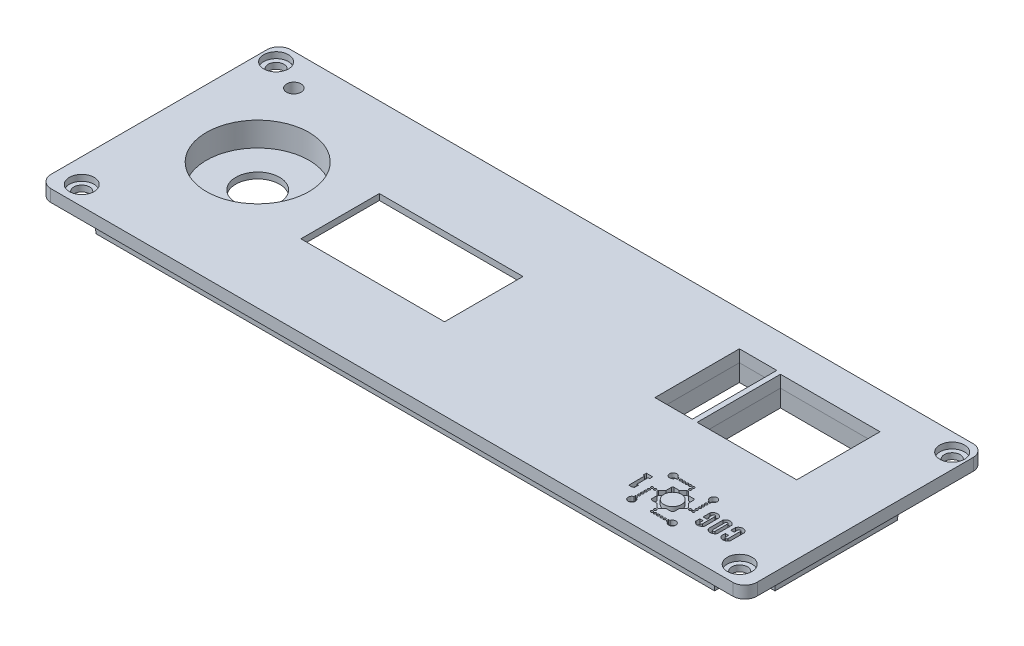
SolidWorks part; units mm, degrees
other "Markup1"
sketch "Sketch25" plane through (-58.5, 2, 19.9) normal (-0.4493, 0.8869, 0.1077) x (-0.8892, -0.4555, 0.042)
other "Markup2"
sketch "Sketch36" plane through (-58.5, -3, -19.8) normal (-0.1656, -0.3822, -0.9091) x (0.9836, -0.1306, -0.1243)
ref_plane "Front Plane" through (0, 0, 0) normal (0, 0, 1) x (1, 0, 0)
ref_plane "Top Plane" through (0, 0, 0) normal (0, 1, 0) x (1, 0, 0)
ref_plane "Right Plane" through (0, 0, 0) normal (1, 0, 0) x (0, 0, -1)
sketch "Sketch1" plane through (0, 0, 0) normal (0, 1, 0) x (1, 0, 0)
  line L0 (58.5, 17.9) -> (58.5, -17.9)
  line L1 (-56.5, 17.9) -> (56.5, 17.9) construction
  line L2 (-56.5, 17.9) -> (-56.5, -17.9) construction
  line L3 (-56.5, -17.9) -> (56.5, -17.9) construction
  line L4 (56.5, 17.9) -> (56.5, -17.9) construction
  line L5 (0, -17.9) -> (0, 17.9) construction
  line L6 (-56.5, 0) -> (56.5, 0) construction
  line L7 (-58.5, 17.9) -> (-58.5, -17.9)
  line L8 (-56.5, -20) -> (56.5, -20)
  line L9 (-56.5, 19.8) -> (56.5, 19.8)
  arc A0 (-56.5, 19.8) -> (-58.5, 17.9) centre (-56.5, 17.7974) ccw
  arc A1 (56.5, 19.8) -> (58.5, 17.9) centre (56.5, 17.7974) cw
  arc A2 (56.5, -20) -> (58.5, -17.9) centre (56.5, -17.9976) ccw
  arc A3 (-58.5, -17.9) -> (-56.5, -20) centre (-56.3975, -17.9) ccw
  circle A7 centre (54.5, -16.85) radius 1.3
  circle A8 centre (56, 16.85) radius 1.3
  circle A9 centre (-56, 16.85) radius 1.3
  circle A10 centre (-54.5, -16.85) radius 1.3
  point P0 (0, 0)
  dimension "D8" = 16.85
  dimension "D1" = 35.8
  dimension "D2" = 113
  dimension "D6" = 1.9
  dimension "D7" = 16.85
  dimension "D9" = 54.5
  dimension "D10" = 56
  dimension "D3" = 2
  dimension "D4" = 2
  dimension "D5" = 2.1
extrude "Boss-Extrude1" add sketch "Sketch1" along normal blind 2
sketch "Sketch3" plane through (0, 0, 0) normal (0, -1, 0) x (1, 0, 0)
  line L4 (0, 0) -> (-65.5905, 0) construction
  line L5 (-51.4, 17.9) -> (51.4, 17.9)
  line L6 (-51.4, 17.9) -> (-51.4, 16.4)
  line L7 (-51.4, 16.4) -> (51.4, 16.4)
  line L8 (56.4, -17.7) -> (56.4, 17.9)
  line L9 (56.4, 17.9) -> (-56.4, 17.9)
  line L10 (-56.4, 17.9) -> (-56.4, -17.7)
  line L11 (-56.4, -17.7) -> (56.4, -17.7)
  line L12 (56.4, -17.7) -> (56.4, 17.9) construction
  line L13 (56.4, 17.9) -> (-56.4, 17.9) construction
  line L14 (-56.4, 17.9) -> (-56.4, -17.7) construction
  line L15 (-56.4, -17.7) -> (56.4, -17.7) construction
  line L16 (51.4, 17.9) -> (51.4, 16.4)
  line L17 (51.4, -17.9) -> (51.4, -16.4)
  line L18 (-51.4, -16.4) -> (51.4, -16.4)
  line L19 (-51.4, -17.9) -> (-51.4, -16.4)
  line L20 (-51.4, -17.9) -> (51.4, -17.9)
  line L21 (0, 0) -> (0, 10.6719) construction
  line L22 (-56.4, 12.9) -> (-54.9, 12.9)
  line L23 (-56.4, 12.9) -> (-56.4, -7.7)
  line L24 (-56.4, -7.7) -> (-54.9, -7.7)
  line L25 (-54.9, 12.9) -> (-54.9, -7.7)
  line L26 (54.9, 12.9) -> (54.9, -7.7)
  line L27 (56.4, -7.7) -> (54.9, -7.7)
  line L28 (56.4, 12.9) -> (56.4, -7.7)
  line L29 (56.4, 12.9) -> (54.9, 12.9)
  point P4 (-51.4, 17.15)
  dimension "D2" = 5
  dimension "D3" = 5
  dimension "D4" = 1.5
  dimension "D5" = 1.5
  dimension "D6" = 10
  dimension "D7" = 5
  dimension "D1" = 2.1
extrude "Boss-Extrude2" add sketch "Sketch3" along normal blind 3 draft 3
sketch "Sketch6" plane through (0, 2, 0) normal (0, 1, 0) x (1, 0, 0)
  circle A15 centre (-56, 16.85) radius 2.05
  circle A16 centre (-56, 16.85) radius 2.05
  circle A18 centre (-54.5, -16.85) radius 2.05
  circle A19 centre (-54.5, -16.85) radius 2.05
  circle A21 centre (54.5, -16.85) radius 2.05
  circle A22 centre (54.5, -16.85) radius 2.05
  circle A24 centre (56, 16.85) radius 2.05
  circle A25 centre (56, 16.85) radius 2.05
  dimension "D1" = 0.75
  dimension "D2" = 0.75
  dimension "D3" = 0.75
  dimension "D4" = 0.75
extrude "Cut-Extrude3" cut sketch "Sketch6" against normal blind 1
sketch "Sketch5" plane through (0, 0, 0) normal (0, -1, 0) x (1, 0, 0)
  line L0 (56.5, -19.8) -> (-56.5, -19.8) construction
  line L1 (-57.5, -10.95) -> (57.5, -10.95) construction
  line L2 (-57.5, -10.95) -> (-57.5, -12.55) construction
  line L3 (-57.5, -12.55) -> (57.5, -12.55) construction
  line L5 (-30.3, 11.9) -> (-3, 11.9) construction
  line L6 (-30.3, 11.9) -> (-30.3, -15.9) construction
  line L7 (-30.3, -15.9) -> (-3, -15.9) construction
  line L8 (-3, 11.9) -> (-3, -15.9) construction
  line L9 (-28.55, 6.5) -> (-4.75, 6.5)
  line L10 (-28.55, 6.5) -> (-28.55, -6.5)
  line L11 (-28.55, -6.5) -> (-4.75, -6.5)
  line L12 (57.5, -10.95) -> (57.5, -12.55) construction
  line L13 (0, -12.55) -> (0, -10.95) construction
  line L14 (-57.5, -11.75) -> (57.5, -11.75) construction
  line L15 (-4.75, 6.5) -> (-4.75, -6.5)
  line L16 (-16.65, -6.5) -> (-16.65, 6.5) construction
  line L17 (-28.55, 0) -> (-4.75, 0) construction
  line L18 (-30.3, 7.63) -> (-3, 7.63) construction
  line L19 (-30.3, 7.63) -> (-30.3, -11.64) construction
  line L20 (-30.3, -11.64) -> (-3, -11.64) construction
  line L21 (-3, 7.63) -> (-3, -11.64) construction
  point P0 (0, -11.75)
  point P11 (-16.65, 0)
  point P16 (-16.65, 11.9)
  dimension "D1" = 115
  dimension "D2" = 1.6
  dimension "D3" = 54.5
  dimension "D4" = 27.3
  dimension "D5" = 27.8
  dimension "D6" = 7.25
  dimension "D7" = 13
  dimension "D8" = 23.8
  dimension "D9" = 1.13
  dimension "D10" = 19.27
  dimension "D11" = 4.27
sketch "Sketch8" plane through (0, 0, 0) normal (0, -1, 0) x (1, 0, 0)
  line L1 (-30.3, 11.9) -> (-3, 11.9)
  line L2 (-30.3, 11.9) -> (-30.3, -15.9)
  line L3 (-30.3, -15.9) -> (-3, -15.9)
  line L4 (-3, 11.9) -> (-3, -15.9)
extrude "Boss-Extrude16" add sketch "Sketch8" along normal blind 0.5
sketch "Sketch9" plane through (0, -0.5, 0) normal (0, -1, 0) x (1, 0, 0)
  line L0 (-30.4, 7.73) -> (-23.8, 7.73)
  line L1 (-23.8, 7.73) -> (-23.8, 11.9)
  line L2 (-30.3, 11.9) -> (-3, 11.9) construction
  line L3 (-23.8, 11.9) -> (-9.5, 11.9)
  line L4 (-3, 11.9) -> (-3, -15.9) construction
  line L6 (-30.4, 7.73) -> (-30.4, -11.84)
  line L8 (-2.9, 7.73) -> (-2.9, -11.84)
  line L9 (-9.5, 11.9) -> (-9.5, 7.73)
  line L11 (-30.3, 11.9) -> (-30.3, -15.9) construction
  line L16 (-9.5, 7.73) -> (-2.9, 7.73)
  line L18 (-30.3, 7.63) -> (-3, 7.63) construction
  line L19 (-30.4, -11.84) -> (-23.8, -11.84)
  line L20 (-23.8, -11.84) -> (-23.8, -15.9)
  line L21 (-30.3, -15.9) -> (-3, -15.9) construction
  line L22 (-23.8, -15.9) -> (-9.5, -15.9)
  line L23 (-9.5, -15.9) -> (-9.5, -11.84)
  line L24 (-9.5, -11.84) -> (-2.9, -11.84)
  dimension "D1" = 0.1
  dimension "D3" = 0.1
  dimension "D4" = 0.1
  dimension "D5" = 6.5
  dimension "D6" = 6.5
extrude "Cut-Extrude8" cut sketch "Sketch9" against normal blind 1.5
sketch "Sketch10" plane through (0, 1, 0) normal (0, -1, 0) x (1, 0, 0)
  line L8 (-4.75, -6.5) -> (-4.75, 6.5)
  line L9 (-28.55, -6.5) -> (-4.75, -6.5)
  line L10 (-28.55, 6.5) -> (-28.55, -6.5)
  line L11 (-4.75, 6.5) -> (-28.55, 6.5)
  line L12 (-4.75, -6.5) -> (-4.75, 6.5)
  line L13 (-28.55, -6.5) -> (-4.75, -6.5)
  line L14 (-28.55, 6.5) -> (-28.55, -6.5)
  line L15 (-4.75, 6.5) -> (-28.55, 6.5)
  dimension "D1" = 0
extrude "Cut-Extrude9" cut sketch "Sketch10" against normal up to surface (1 mm away) up to face at (-56, 2, -14.8)
sketch "Sketch11" plane through (0, -0.5, 0) normal (0, -1, 0) x (1, 0, 0)
  line L1 (-30.3, 11.9) -> (-30.3, -15.9) construction
  line L2 (-3, 11.9) -> (-3, -15.9) construction
  line L3 (-30.3, 9.9) -> (-3, 9.9) construction
  line L5 (-30.3, 11.9) -> (-3, 11.9) construction
  line L6 (-30.3, -15.9) -> (-3, -15.9) construction
  line L7 (-5, -15.9) -> (-5, 11.9) construction
  line L8 (-16.65, 6.5) -> (-16.65, -8.5129) construction
  circle A0 centre (-5, 9.9) radius 0.8
  circle A3 centre (-28.3, 9.9) radius 0.8
  dimension "D4" = 1.6
  dimension "D1" = 2
  dimension "D3" = 2
extrude "Boss-Extrude6" add sketch "Sketch11" along normal blind 1.2
fillet "Fillet1" radius 0.6 2 edges at (-5, -1.7, 9.1) (-28.3, -1.7, 10.7)
sketch "Sketch13" plane through (0, 0, 0) normal (0, -1, 0) x (1, 0, 0)
  line L0 (-57.5, -10.95) -> (-57.5, -12.55) construction
  line L1 (-57.5, -10.95) -> (57.5, -10.95) construction
  line L2 (-57.5, -12.55) -> (57.5, -12.55) construction
  circle A0 centre (-43.15, -0.95) radius 8 construction
  circle A2 centre (-43.15, -0.95) radius 8.5
  circle A4 centre (-50.77, -14.55) radius 1.2
  dimension "D2" = 16
  dimension "D8" = 2.4
  dimension "D9" = 6.73
  dimension "D1" = 14.35
  dimension "D3" = 10
  dimension "D10" = 2
  dimension "D7" = 0.5
extrude "Cut-Extrude10" cut sketch "Sketch13" against normal up to surface (2 mm away) up to face at (-16.65, 2, 0)
sketch "Sketch16" plane through (0, 2, 0) normal (0, 1, 0) x (1, 0, 0)
  line L0 (-4.3168, 26.8231) -> (81.0165, 26.8231) construction
  line L1 (50.3534, -14.2896) -> (50.3534, -11.9125)
  line L2 (48.878, -11.9125) -> (48.878, -12.6953)
  line L3 (48.878, -12.6953) -> (49.433, -12.6953)
  line L4 (49.433, -12.6953) -> (49.433, -12.0324)
  line L5 (49.8354, -12.0324) -> (49.8354, -14.1204)
  line L6 (49.433, -14.1204) -> (49.433, -13.6115)
  line L7 (49.433, -13.6115) -> (48.878, -13.6115)
  line L8 (48.878, -13.6115) -> (48.878, -14.2896)
  line L9 (48.2412, -14.2896) -> (48.2412, -11.9125)
  line L10 (46.7671, -11.9125) -> (46.7671, -14.2896)
  line L11 (47.7035, -12.0324) -> (47.7035, -14.1204)
  line L12 (47.3081, -14.1204) -> (47.3081, -12.0324)
  line L13 (46.1267, -14.2896) -> (46.1267, -11.9125)
  line L14 (44.6639, -11.9125) -> (44.6639, -13.0881)
  line L15 (44.6639, -13.0881) -> (45.3238, -13.0881)
  line L16 (45.3238, -13.0881) -> (45.3238, -12.6953)
  line L17 (45.3238, -12.6953) -> (45.2014, -12.6953)
  line L18 (45.2014, -12.6953) -> (45.2014, -12.0324)
  line L19 (45.5941, -12.0324) -> (45.5941, -14.1204)
  line L20 (45.2014, -14.1204) -> (45.2014, -13.6115)
  line L21 (45.2014, -13.6115) -> (44.6639, -13.6115)
  line L22 (44.6639, -13.6115) -> (44.6639, -14.2896)
  line L44 (40.4042, -14.9356) -> (41.3098, -14.9356)
  line L45 (41.3098, -14.9356) -> (41.4866, -14.7588)
  line L46 (41.4866, -14.7588) -> (41.4866, -13.8532)
  line L50 (42.4261, -16.72) -> (42.1504, -16.72)
  line L51 (42.1504, -16.72) -> (42.1504, -16.3239)
  line L52 (42.1504, -16.3239) -> (42.4211, -16.3239)
  line L53 (36.0066, -15.8752) -> (36.0066, -15.5994)
  line L54 (36.4027, -15.5994) -> (36.4027, -15.8701)
  line L55 (36.0066, -15.5994) -> (36.4027, -15.5994)
  line L56 (36.8515, -9.4557) -> (37.1272, -9.4557)
  line L57 (37.1272, -9.8518) -> (36.8565, -9.8518)
  line L58 (37.1272, -9.4557) -> (37.1272, -9.8518)
  line L59 (43.271, -10.3005) -> (43.271, -10.5763)
  line L60 (42.8749, -10.5763) -> (42.8749, -10.3055)
  line L61 (43.271, -10.5763) -> (42.8749, -10.5763)
  line L62 (34.7503, -11.5007) -> (34.7503, -12.0307)
  line L63 (34.7503, -12.0307) -> (34.4877, -12.0307)
  line L64 (34.4877, -12.0307) -> (34.4877, -13.8706)
  line L65 (34.4877, -13.8706) -> (34.7503, -13.8706)
  line L66 (34.7503, -13.8706) -> (34.7503, -14.5384)
  line L67 (34.7503, -14.5384) -> (34.4877, -14.6755)
  line L68 (34.4877, -14.6755) -> (33.9483, -14.6755)
  line L69 (33.9483, -14.6755) -> (33.9483, -12.0307)
  line L70 (33.9483, -12.0307) -> (33.682, -12.0307)
  line L71 (33.682, -12.0307) -> (33.682, -11.5007)
  line L72 (33.682, -11.5007) -> (34.7503, -11.5007)
  line L73 (39.6388, -13.0878) -> (40.774, -15.8285) construction
  line L74 (40.774, -15.8285) -> (40.4042, -14.9356) construction
  line L75 (39.6388, -13.0878) -> (42.5677, -14.301) construction
  line L76 (39.6388, -13.0878) -> (39.6388, -15.4936) construction
  line L77 (39.6388, -13.0878) -> (40.8661, -14.3151) construction
  line L78 (42.0125, -13.5426) -> (40.0416, -15.5135) construction
  line L79 (38.8734, -14.9356) -> (39.5138, -15.576)
  line L80 (39.5138, -15.576) -> (39.7638, -15.576)
  line L82 (37.791, -13.8532) -> (37.791, -14.7588)
  line L83 (37.791, -14.7588) -> (37.9678, -14.9356)
  line L84 (37.9678, -14.9356) -> (38.8734, -14.9356)
  line L85 (37.791, -12.3225) -> (37.1507, -12.9628)
  line L86 (37.1507, -12.9628) -> (37.1507, -13.2128)
  line L87 (37.1507, -13.2128) -> (37.791, -13.8532)
  line L88 (38.8734, -11.2401) -> (37.9678, -11.2401)
  line L89 (37.9678, -11.2401) -> (37.791, -11.4169)
  line L90 (37.791, -11.4169) -> (37.791, -12.3225)
  line L91 (40.4042, -11.2401) -> (39.7638, -10.5997)
  line L92 (39.7638, -10.5997) -> (39.5138, -10.5997)
  line L93 (39.5138, -10.5997) -> (38.8734, -11.2401)
  line L94 (41.4866, -12.3225) -> (41.4866, -11.4169)
  line L95 (41.4866, -11.4169) -> (41.3098, -11.2401)
  line L96 (41.3098, -11.2401) -> (40.4042, -11.2401)
  line L97 (41.4866, -13.8532) -> (42.1269, -13.2128)
  line L98 (42.1269, -13.2128) -> (42.1269, -12.9628)
  line L99 (42.1269, -12.9628) -> (41.4866, -12.3225)
  line L100 (39.7638, -15.576) -> (40.4042, -14.9356) [skipped]
  line L101 (40.4042, -14.9356) -> (39.7638, -15.576)
  arc A0 (50.3534, -14.2896) -> (48.878, -14.2896) centre (49.6157, -13.9163) cw
  arc A1 (49.8354, -14.1204) -> (49.433, -14.1204) centre (49.6342, -14.0961) cw
  arc A2 (49.433, -12.0324) -> (49.8354, -12.0324) centre (49.6342, -12.0817) cw
  arc A3 (48.878, -11.9125) -> (50.3534, -11.9125) centre (49.6157, -12.2024) cw
  arc A4 (47.3081, -12.0324) -> (47.7035, -12.0324) centre (47.5058, -12.0768) cw
  arc A5 (47.7035, -14.1204) -> (47.3081, -14.1204) centre (47.5058, -14.0752) cw
  arc A6 (48.2412, -14.2896) -> (46.7671, -14.2896) centre (47.5042, -13.9187) cw
  arc A7 (46.7671, -11.9125) -> (48.2412, -11.9125) centre (47.5042, -12.2159) cw
  arc A8 (46.1267, -14.2896) -> (44.6639, -14.2896) centre (45.3953, -13.9241) cw
  arc A9 (44.6639, -11.9125) -> (46.1267, -11.9125) centre (45.3953, -12.197) cw
  arc A10 (45.2014, -12.0324) -> (45.5941, -12.0324) centre (45.3977, -12.071) cw
  arc A11 (45.5941, -14.1204) -> (45.2014, -14.1204) centre (45.3977, -14.0769) cw
  circle A13 centre (39.6388, -13.0878) radius 1.4609
  arc A14 (42.4211, -16.3239) -> (42.4261, -16.72) centre (42.9899, -16.5147) cw
  circle A15 centre (41.7559, -16.5245) radius 0.2
  circle A16 centre (41.2259, -16.5245) radius 0.2
  circle A17 centre (40.6959, -16.5245) radius 0.2
  circle A18 centre (40.1659, -16.5245) radius 0.2
  circle A19 centre (39.6359, -16.5245) radius 0.2
  circle A20 centre (39.6359, -15.9945) radius 0.2
  arc A21 (36.4027, -15.8701) -> (36.0066, -15.8752) centre (36.2119, -16.439) cw
  circle A22 centre (36.2021, -15.205) radius 0.2
  circle A23 centre (36.2021, -14.675) radius 0.2
  circle A24 centre (36.2021, -14.145) radius 0.2
  circle A25 centre (36.2021, -13.615) radius 0.2
  circle A26 centre (36.2021, -13.085) radius 0.2
  circle A27 centre (36.7321, -13.085) radius 0.2
  arc A28 (36.8565, -9.8518) -> (36.8515, -9.4557) centre (36.2877, -9.6609) cw
  circle A29 centre (37.5217, -9.6511) radius 0.2
  circle A30 centre (38.0517, -9.6511) radius 0.2
  circle A31 centre (38.5817, -9.6511) radius 0.2
  circle A32 centre (39.1117, -9.6511) radius 0.2
  circle A33 centre (39.6417, -9.6511) radius 0.2
  circle A34 centre (39.6417, -10.1811) radius 0.2
  arc A35 (42.8749, -10.3055) -> (43.271, -10.3005) centre (43.0657, -9.7367) cw
  circle A36 centre (43.0755, -10.9707) radius 0.2
  circle A37 centre (43.0755, -11.5007) radius 0.2
  circle A38 centre (43.0755, -12.0307) radius 0.2
  circle A39 centre (43.0755, -12.5607) radius 0.2
  circle A40 centre (43.0755, -13.0907) radius 0.2
  circle A41 centre (42.5455, -13.0907) radius 0.2
  circle A42 centre (39.6388, -13.0878) radius 2 construction
  point P146 (39.6388, -13.0878)
  point P171 (39.6388, -13.0878)
  dimension "D1" = 5
  dimension "D4" = 0.4
  dimension "D5" = 0.6
  dimension "D6" = 4
  dimension "D7" = 22.5
  dimension "D8" = 45
  dimension "D9" = 45
  dimension "D10" = 0.25
  dimension "D2" = 2
  dimension "D3" = 4
  dimension "D11" = 8
extrude "Cut-Extrude11" cut sketch "Sketch16" against normal blind 0.75
sketch "Sketch29" plane through (0, 0, 0) normal (0, -1, 0) x (1, 0, 0)
  line L0 (-50.77, -15.5) -> (-51.27, -16.5)
  line L1 (-51.27, -16.5) -> (-50.27, -16.5)
  line L2 (-50.27, -16.5) -> (-50.77, -15.5)
  line L3 (-51.72, -14.55) -> (-52.72, -14.05)
  line L4 (-52.72, -14.05) -> (-52.72, -15.05)
  line L5 (-52.72, -15.05) -> (-51.72, -14.55)
  line L6 (-50.77, -13.6) -> (-50.27, -12.6)
  line L7 (-50.27, -12.6) -> (-51.27, -12.6)
  line L8 (-51.27, -12.6) -> (-50.77, -13.6)
  line L9 (-49.82, -14.55) -> (-48.82, -15.05)
  line L10 (-48.82, -15.05) -> (-48.82, -14.05)
  line L11 (-48.82, -14.05) -> (-49.82, -14.55)
  circle A0 centre (-50.77, -14.55) radius 0.95 construction
  circle A1 centre (-50.77, -14.55) radius 1.2 construction
  point P8 (-50.77, -16.5)
  point P21 (-50.77, -14.55)
  dimension "D1" = 1.9
  dimension "D2" = 1
  dimension "D3" = 1
  dimension "D4" = 4
extrude "Boss-Extrude17" add sketch "Sketch29" along normal blind 3
sketch "Sketch34" plane through (0, 0, 0) normal (0, -1, 0) x (1, 0, 0)
  line L0 (-51.5494, -12.6) -> (-49.9906, -12.6)
  line L1 (-50.27, -12.6) -> (-51.27, -12.6) construction
  circle A0 centre (-50.77, -14.55) radius 1.4
  arc A2 (-49.9906, -12.6) -> (-51.5494, -12.6) centre (-50.77, -14.55) cw
  dimension "D1" = 2.8
  dimension "D2" = 0.7
sketch "Sketch26" plane through (0, 0, 2) normal (0, 1, 0) x (1, 0, 0)
  line L0 (58.5, -15.9) -> (58.5, 19.9) construction
  line L9 (56.5, 21.8) -> (-56.5, 21.8) construction
  line L18 (3.7694, 6.3) -> (11.4293, 6.3)
  line L19 (3.7694, 6.3) -> (3.7694, 1.3)
  line L20 (3.7694, 1.3) -> (11.4293, 1.3)
  line L21 (11.4293, 6.3) -> (11.4293, 1.3)
  line L23 (15.4, 12.8) -> (20.6, 12.8)
  line L24 (15.4, 12.8) -> (15.4, 1.3)
  line L25 (15.4, 1.3) -> (20.6, 1.3)
  line L26 (20.6, 12.8) -> (20.6, 1.3)
  dimension "D1" = 7.6599
  dimension "D2" = 5
  dimension "D3" = 37.9
  dimension "D4" = 3.9707
  dimension "D5" = 15.5
  dimension "D6" = 5.2
  dimension "D7" = 11.5
  dimension "D8" = 9
sketch "Sketch23" plane through (0, 0, 0) normal (0, -1, 0) x (1, 0, 0)
  circle A0 centre (-43.15, -0.95) radius 8.5
  circle A1 centre (-43.15, -0.95) radius 8.5 construction
  circle A2 centre (-43.15, -0.95) radius 9.5
  dimension "D1" = 1
extrude "Boss-Extrude9" add sketch "Sketch23" along normal blind 3
sketch "Sketch24" plane through (0, -3, 0) normal (0, -1, 0) x (1, 0, 0)
  circle A0 centre (-43.15, -0.95) radius 9.5
  circle A1 centre (-43.15, -0.95) radius 9.5 construction
  circle A2 centre (-43.15, -0.95) radius 3.625
  dimension "D1" = 7.25
extrude "Boss-Extrude10" add sketch "Sketch24" against normal blind 1
sketch "Sketch20" plane through (0, 2, 0) normal (0, 1, 0) x (1, 0, 0)
  line L0 (58.5, -17.9) -> (58.5, 17.9) construction
  line L1 (47.1, 0) -> (30.6, 0)
  line L2 (47.1, 0) -> (47.1, 13.8)
  line L3 (47.1, 13.8) -> (30.6, 13.8)
  line L4 (30.6, 0) -> (30.6, 13.8)
  line L8 (56.5, 19.8) -> (-56.5, 19.8) construction
  line L10 (29.75, 0.05) -> (23.55, 0.05)
  line L11 (29.75, 0.05) -> (29.75, 14.05)
  line L12 (29.75, 14.05) -> (23.55, 14.05)
  line L13 (23.55, 0.05) -> (23.55, 14.05)
  dimension "D1" = 11.4
  dimension "D2" = 6
  dimension "D3" = 13.8
  dimension "D4" = 16.5
  dimension "D5" = 6.2
  dimension "D6" = 14
  dimension "D7" = 0.85
  dimension "D12" = 5.75
extrude "Cut-Extrude14" cut sketch "Sketch20" against normal through all both and the other way through all
extrude "Cut-Extrude16" cut sketch "Sketch26" along normal offset from surface (1 mm away) 1 up to face at (38.85, 2, -6.9)
ref_plane "Plane1" through (-16.65, 0, 0) normal (1, 0, 0) x (0, 0, 1)
sketch "Sketch30" plane through (-16.65, 0, 0) normal (1, 0, 0) x (0, 0, 1)
  line L0 (-16.4917, 1.75) -> (-16.5441, 2.75)
  line L1 (-16.5572, 3) -> (-16.4, 0) construction
  line L3 (-16.2417, 1.75) -> (-16.4917, 1.75)
  line L4 (-16.5441, 2.75) -> (-16.0917, 2.75)
  line L5 (-15.7417, 2.4) -> (-15.7417, 2.25)
  line L6 (-15.9, 0.5) -> (-11.84, 0.5) construction
  arc A0 (-15.7417, 2.25) -> (-16.2417, 1.75) centre (-16.2417, 2.25) cw
  arc A1 (-16.0917, 2.75) -> (-15.7417, 2.4) centre (-16.0917, 2.4) cw
  point P7 (-15.7417, 1.75)
  dimension "D3" = 0.5
  dimension "D2" = 0.35
  dimension "D1" = 0.75
  dimension "D4" = 1.25
  dimension "D5" = 1
extrude "Boss-Extrude20" add sketch "Sketch30" against normal up to surface (27.3 mm away) from surface at 13.65 up to face at (-30.3, -0.25, -13.87) starting at face at (-3, -0.25, -13.87)
sketch "Sketch33" plane through (0, 0, 0) normal (0, -1, 0) x (1, 0, 0)
  line L0 (23.55, -0.25) -> (22.55, -0.25)
  line L1 (22.55, -0.25) -> (22.55, -15.05)
  line L2 (22.55, -15.05) -> (48.1, -15.05)
  line L3 (48.1, -15.05) -> (48.1, -0.25)
  line L4 (48.1, -0.25) -> (47.1, -0.25)
  line L5 (47.1, -0.25) -> (47.1, -13.8)
  line L6 (47.1, -13.8) -> (30.6, -13.8)
  line L7 (30.6, -13.8) -> (30.6, -0.25)
  line L8 (30.6, -0.25) -> (29.75, -0.25)
  line L9 (29.75, -0.25) -> (29.75, -14.05)
  line L10 (29.75, -14.05) -> (23.55, -14.05)
  line L11 (23.55, -14.05) -> (23.55, -0.25)
  line L12 (23.55, -0.05) -> (23.55, -14.05) construction
  line L14 (47.1, 0) -> (30.6, 0) construction
  line L15 (47.1, 0) -> (47.1, -13.8) construction
  line L16 (29.75, -0.05) -> (29.75, -14.05) construction
  line L17 (30.6, 0) -> (30.6, -13.8) construction
  dimension "D1" = 1
  dimension "D2" = 1
  dimension "D3" = 1
  dimension "D4" = 0.25
extrude "Boss-Extrude22" add sketch "Sketch33" along normal up to surface (3 mm away) draft 3
extrude "Boss-Extrude23" add sketch "Sketch34" along normal up to surface (3 mm away) up to face at (-52.3867, -3, -14.55)
ref_plane "Plane3" through (0, -1.8, 0) normal (0, -1, 0) x (-1, 0, 0)
sketch "Sketch35" plane through (0, -1.8, 0) normal (0, -1, 0) x (-1, 0, 0)
  line L0 (14.65, -16.5572) -> (18.65, -16.5572)
  line L4 (16.65, 6.5) -> (16.65, -6.5) construction
  line L5 (18.65, -16.5572) -> (30.3, -10.4)
  line L6 (30.3, -10.4) -> (30.3, -9.2689)
  line L7 (30.3, -9.2689) -> (19.6971, -14.8727)
  line L8 (19.6971, -14.8727) -> (13.6029, -14.8727)
  line L9 (13.6029, -14.8727) -> (3, -9.2689)
  line L10 (3, -11.9) -> (3, 15.9) construction
  line L11 (3, -9.2689) -> (3, -10.4)
  line L12 (3, -10.4) -> (14.65, -16.5572)
  line L13 (30.3, -11.9) -> (30.3, 15.9) construction
  line L14 (51.2428, -16.5572) -> (-51.2428, -16.5572) construction
  point P6 (16.65, -16.5572)
  dimension "D1" = 4
  dimension "D2" = 1
  dimension "D3" = 1.5
extrude "Boss-Extrude24" add sketch "Sketch35" along normal up to surface (1.2 mm away) up to face at (0, -3, 17.15)
fillet "Fillet2" radius 0.5 8 edges at (-3, -2.4, 9.2689) (-3, -2.4, 10.4) (-30.3, -2.4, 10.4) (-30.3, -2.4, 9.2689) (-19.6971, -2.4, 14.8727) (-13.6029, -2.4, 14.8727) (-14.5905, -2.4, 16.5258) (-18.7095, -2.4, 16.5258)
